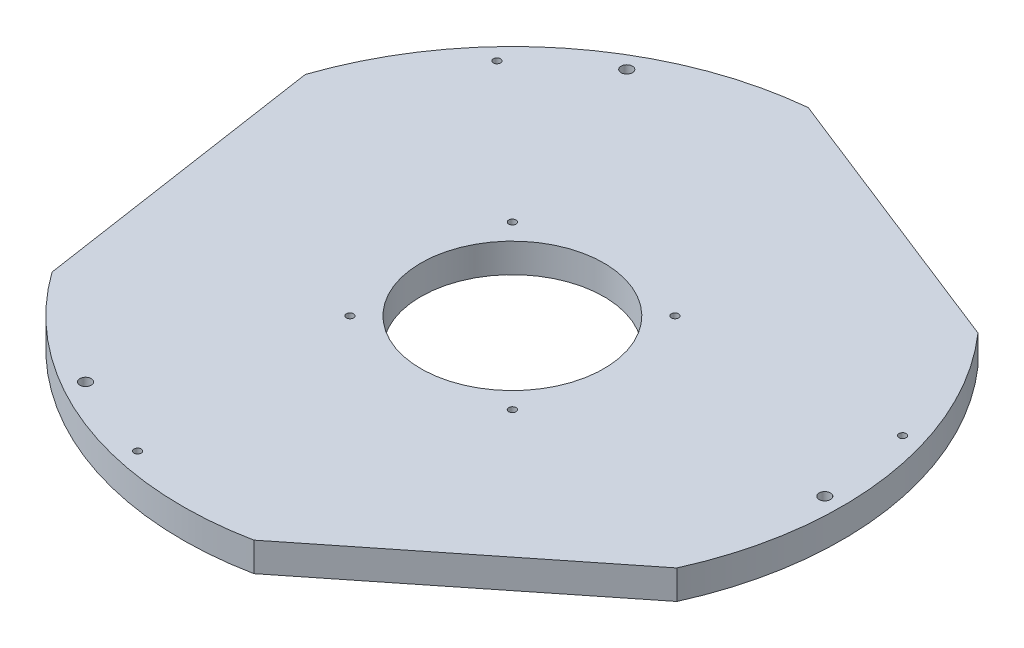
SolidWorks part; units mm, degrees
material "Oak"
ref_plane "Front Plane" through (0, 0, 0) normal (0, 0, 1) x (1, 0, 0)
ref_plane "Top Plane" through (0, 0, 0) normal (0, 1, 0) x (1, 0, 0)
ref_plane "Right Plane" through (0, 0, 0) normal (1, 0, 0) x (0, 0, -1)
sketch "Sketch1" plane through (0, 0, 0) normal (0, 0, 1) x (1, 0, 0)
  line L0 (0, -200000) -> (0, 218797.9879) construction
  line L1 (144.145, -24.4122) -> (144.145, -37.1122) construction
  line L2 (0, -24.4122) -> (144.145, -24.4122) construction
  line L3 (144.145, -37.1122) -> (0, -37.1122) construction
  line L4 (0, -200000) -> (0, 218797.9879) construction
  line L5 (144.145, -24.4122) -> (144.145, -37.1122)
  line L6 (0, -24.4122) -> (144.145, -24.4122)
  line L7 (144.145, -37.1122) -> (0, -37.1122)
  line L8 (0, -24.4122) -> (0, -37.1122)
revolve "Revolve1" add sketch "Sketch1" angle 360 about L4
hole_wizard "1/8 (0.125) Diameter Hole1" positions "Sketch2" profile "Sketch3" hole size "1/8" standard "ANSI Inch" end condition up to next
sketch "Sketch2" plane through (0, -24.4122, 0) normal (0, 1, 0) x (1, 0, 0)
  line L0 (0, 0) -> (136.525, 0) construction
  line L3 (0, 0) -> (-68.2625, -118.2341) construction
  line L6 (0, 0) -> (-68.2625, 118.2341) construction
  line L7 (-99.8481, 93.1098) -> (0, 0) construction
  line L9 (0, 0) -> (-30.7114, -133.0259) construction
  line L12 (0, 0) -> (130.5595, 39.916) construction
  line L14 (-35.5, -35.5) -> (35.5, -35.5) construction
  line L15 (-35.5, -35.5) -> (-35.5, 35.5) construction
  line L16 (-35.5, 35.5) -> (35.5, 35.5) construction
  line L17 (35.5, -35.5) -> (35.5, 35.5) construction
  line L18 (-35.5, 0) -> (0, 0) construction
  line L19 (0, 0) -> (0, -35.5) construction
  circle A0 centre (0, 0) radius 136.525
  point P0 (136.525, 0)
  point P2 (-68.2625, -118.2341)
  point P4 (-68.2625, 118.2341)
  point P32 (-99.8481, 93.1098)
  point P57 (130.5595, 39.916)
  point P60 (-30.7114, -133.0259)
  point P138 (-35.5, -35.5)
  point P141 (-35.5, 35.5)
  point P144 (35.5, 35.5)
  point P147 (35.5, -35.5)
  dimension "D3" = 17
  dimension "D1" = 120
  dimension "D2" = 120
  dimension "D4" = 120
  dimension "D5" = 120
  dimension "D6" = 71
sketch "Sketch3" plane through (136.525, -24.4122, 0) normal (1, 0, 0) x (0, 0, 1)
  line L0 (0, 0) -> (0, 12.7)
  line L1 (0, 12.7) -> (1.5875, 12.7)
  line L2 (1.5875, 12.7) -> (1.5875, 0)
  line L5 (1.5875, 0) -> (0, 0)
  line L11 (0, -6.35) -> (0, 107.95) construction
  dimension "Thru Hole Dia." = 3.175
  dimension "Thru Hole Depth" = 12.7
sketch "Sketch4" plane through (0, -24.4122, 0) normal (0, 1, 0) x (1, 0, 0)
  line L0 (253.7221, 37.919) -> (-94.0222, -238.6893)
  line L1 (-94.0222, -238.6893) -> (-159.6999, 200.7703)
  line L2 (-159.6999, 200.7703) -> (253.7221, 37.919)
  line L3 (253.7221, 37.919) -> (0, 0) construction
  line L4 (130.5595, 39.916) -> (136.525, 0) construction
  circle A0 centre (0, 0) radius 128.27 construction
  point P6 (133.5423, 19.958)
  dimension "D1" = 256.54
extrude "Cut-Extrude1" cut sketch "Sketch4" against normal through all flip side to cut
sketch "Sketch6" plane through (0, -24.4122, 0) normal (0, 1, 0) x (1, 0, 0)
  circle A0 centre (0, 0) radius 40
  dimension "D1" = 80
extrude "Cut-Extrude2" cut sketch "Sketch6" against normal through all
hole_wizard "M6x1.0 Tapped Hole1" positions "Sketch7" profile "Sketch8" tap size "M6x1.0" standard "ANSI Metric" end condition through all
sketch "Sketch7" plane through (0, -24.4122, 0) normal (0, 1, 0) x (1, 0, 0)
  point P0 (-68.2625, 118.2341)
  point P4 (136.525, 0)
  point P8 (-68.2625, -118.2341)
  point P12 (0, 0)
  point P13 (136.525, 0)
  point P15 (0, 0)
  point P16 (-68.2625, 118.2341)
sketch "Sketch8" plane through (-68.2625, -24.4122, -118.2341) normal (1, 0, 0) x (0, 0, 1)
  line L0 (0, 0) -> (0, 12.7)
  line L1 (0, 12.7) -> (2.5, 12.7)
  line L2 (2.5, 12.7) -> (2.5, 0)
  line L5 (2.5, 0) -> (0, 0)
  line L11 (0, -6.35) -> (0, 107.95) construction
  dimension "Thru Tap Drill Dia." = 5
  dimension "Thru Tap Drill Depth" = 12.7
cosmetic thread "Hole Thread1" parameters "D2"=6
cosmetic thread "Hole Thread2" parameters "D2"=6
cosmetic thread "Hole Thread3" parameters "D2"=6
